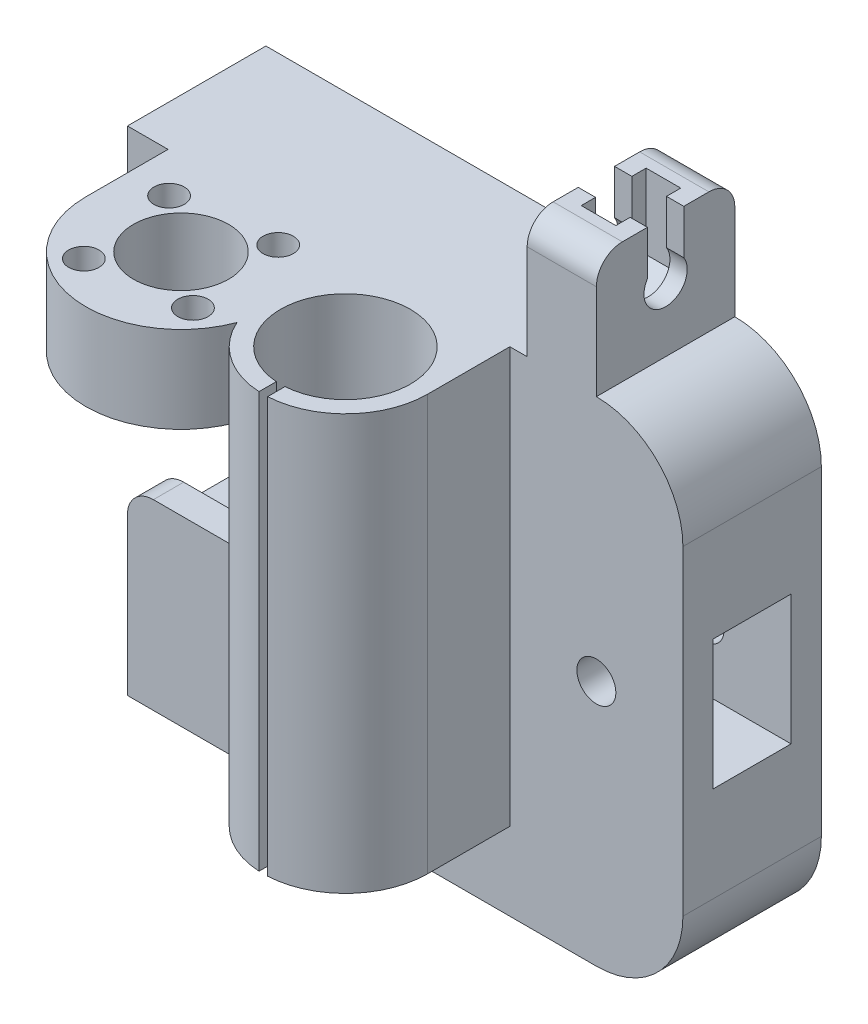
SolidWorks part; units mm, degrees
ref_plane "Front Plane" through (0, 0, 0) normal (0, 0, 1) x (1, 0, 0)
ref_plane "Top Plane" through (0, 0, 0) normal (0, 1, 0) x (1, 0, 0)
ref_plane "Right Plane" through (0, 0, 0) normal (1, 0, 0) x (0, 0, -1)
sketch "Sketch1" plane through (0, 0, 0) normal (0, 1, 0) x (1, 0, 0)
  line L0 (0, 0) -> (64.191, 0)
  line L1 (64.191, 0) -> (64.191, -16)
  line L2 (34.191, -32.9833) -> (34.191, -34.9868)
  line L3 (0, 0) -> (0, -16)
  line L4 (15.691, -25.5) -> (34.691, -25.5) construction
  line L5 (15.691, -25.5) -> (15.691, 0) construction
  line L6 (15.691, -25.5) -> (15.691, -33.5) construction
  line L7 (10.7657, -31.8041) -> (20.6163, -19.1959) construction
  line L8 (9.3869, -20.5747) -> (21.9951, -30.4253) construction
  line L9 (35.191, -32.9833) -> (35.191, -34.9868)
  line L10 (34.691, -25.5) -> (34.691, -32.9833) construction
  line L11 (34.191, -32.9833) -> (35.191, -32.9833) construction
  line L12 (34.191, -34.9868) -> (35.191, -34.9868) construction
  line L13 (64.191, -16) -> (44.191, -16)
  line L14 (44.191, -16) -> (44.191, -25.5)
  line L15 (0, -16) -> (4.691, -16)
  line L16 (4.691, -16) -> (4.691, -25.5)
  circle A0 centre (15.691, -25.5) radius 5.5
  arc A1 (35.191, -32.9833) -> (34.191, -32.9833) centre (34.691, -25.5) ccw
  arc A2 (35.191, -34.9868) -> (44.191, -25.5) centre (34.691, -25.5) ccw
  circle A3 centre (15.691, -25.5) radius 8 construction
  circle A4 centre (10.7657, -31.8041) radius 1.75
  circle A5 centre (9.3869, -20.5747) radius 1.75
  circle A6 centre (20.6163, -19.1959) radius 1.75
  circle A7 centre (21.9951, -30.4253) radius 1.75
  arc A8 (4.691, -25.5) -> (26.0002, -29.3367) centre (15.691, -25.5) ccw
  arc A9 (26.0002, -29.3367) -> (34.191, -34.9868) centre (34.691, -25.5) ccw
  dimension "D1" = 19
  dimension "D2" = 15
  dimension "D3" = 11
  dimension "D5" = 2
  dimension "D6" = 16
  dimension "D7" = 38
  dimension "D8" = 3.5
  dimension "D9" = 22
  dimension "D10" = 1
  dimension "D4" = 25.5
  dimension "D11" = 16
  dimension "D12" = 20
  dimension "D13" = 4.691
extrude "Boss-Extrude1" add sketch "Sketch1" along normal mid plane 57 contours A8 A2 L0 | A2 A8 A0 A4 A5 A6 A7 | A8 A2 L2 A1 L9 | A2 A8 region at (29.3649, 0, 12.581)
sketch "Sketch2" plane through (0, 0, 16) normal (0, 0, 1) x (1, 0, 0)
  line L0 (4.691, 28.5) -> (4.691, -28.5) construction
  line L1 (4.691, 18.5) -> (26.0002, 18.5)
  line L2 (4.691, 18.5) -> (4.691, -28.5)
  line L3 (4.691, -28.5) -> (44.191, -28.5)
  line L5 (26.0002, 28.5) -> (4.691, 28.5) construction
  line L6 (26.0002, 18.5) -> (26.0002, -19.5)
  line L7 (26.0002, -19.5) -> (44.191, -19.5)
  line L8 (44.191, 28.5) -> (44.191, -28.5) construction
  line L9 (44.191, -19.5) -> (44.191, -28.5)
  dimension "D1" = 10
  dimension "D2" = 9
  dimension "D3" = 21.3092
extrude "Cut-Extrude1" cut sketch "Sketch2" along normal through all
sketch "Sketch3" plane through (0, 0, 0) normal (-1, 0, 0) x (0, 0, 1)
  line L0 (8, 28.5) -> (8, 12.5) construction
  line L1 (3.5, 12.5) -> (12.5, 12.5)
  line L2 (3.5, 12.5) -> (3.5, -12.5)
  line L3 (3.5, -12.5) -> (12.5, -12.5)
  line L4 (12.5, 12.5) -> (12.5, -12.5)
  line L5 (0, 28.5) -> (16, 28.5) construction
  line L6 (0, 0) -> (3.5, 0) construction
  line L7 (0, 28.5) -> (0, -28.5) construction
  line L8 (0, -28.5) -> (16, -28.5) construction
  dimension "D1" = 3.5
  dimension "D2" = 16
  dimension "D3" = 25
extrude "Cut-Extrude2" cut sketch "Sketch3" against normal blind 28
sketch "Sketch4" plane through (0, 0, 0) normal (-1, 0, 0) x (0, 0, 1)
  line L0 (16, 28.5) -> (16, -28.5) construction
  line L1 (0, 7.4) -> (16, 7.4)
  line L2 (0, 7.4) -> (0, -7.4)
  line L3 (0, -7.4) -> (16, -7.4)
  line L4 (16, 7.4) -> (16, -7.4)
  point P4 (0, 0)
  point P9 (8, 7.4)
  dimension "D1" = 14.8
extrude "Cut-Extrude3" cut sketch "Sketch4" against normal up to surface (26.0002 mm away) up to face at (26.0002, -0.5, 22.6683)
hole_wizard "M4 Clearance Hole1" positions "3DSketch1" profile "Sketch5" hole size "M4" standard "ANSI Metric" end condition through all
sketch3d "3DSketch1"
  line L0 (54.191, 0, 16) -> (64.191, 0, 16) construction
  line L6 (64.191, 28.5, 16) -> (64.191, -28.5, 16) construction
  point P0 (54.191, 0, 16)
  dimension "D1" = 10
sketch "Sketch5" plane through (54.191, 0, 16) normal (1, 0, 0) x (0, -1, 0)
  line L0 (0, 0) -> (0, 16)
  line L1 (0, 16) -> (2.25, 16)
  line L2 (2.25, 16) -> (2.25, 0)
  line L5 (2.25, 0) -> (0, 0)
  line L11 (0, -6.35) -> (0, 107.95) construction
  dimension "Thru Hole Dia." = 4.5
  dimension "Thru Hole Depth" = 16
sketch "Sketch6" plane through (0, 0, 0) normal (-1, 0, 0) x (0, 0, 1)
  line L0 (8, -22.5) -> (8, 22.5) construction
  line L1 (8, 22.5) -> (8, 28.5) construction
  line L2 (8, -22.5) -> (8, -28.5) construction
  line L3 (0, -28.5) -> (16, -28.5) construction
  line L4 (0, 28.5) -> (16, 28.5) construction
  circle A0 centre (8, 22.5) radius 4.1
  circle A1 centre (8, -22.5) radius 4.1
  dimension "D1" = 45
  dimension "D2" = 8.2
extrude "Cut-Extrude4" cut sketch "Sketch6" against normal blind 20 contours A1 | A0 | A0 region at (0, 22.5, 8) region at (0, -22.5, 8)
sketch "Sketch7" plane through (28, 0, 0) normal (-1, 0, 0) x (0, 0, 1)
  line L0 (0, 0) -> (3.5, 0) construction
  line L1 (3.5, 7.5) -> (12.5, 7.5)
  line L2 (3.5, 7.5) -> (3.5, -7.5)
  line L3 (3.5, -7.5) -> (12.5, -7.5)
  line L4 (12.5, 7.5) -> (12.5, -7.5)
  line L5 (8, 7.5) -> (8, 12.5) construction
  line L6 (12.5, 12.5) -> (3.5, 12.5) construction
  line L7 (12.5, -12.5) -> (12.5, 12.5) construction
  dimension "D1" = 15
extrude "Cut-Extrude5" cut sketch "Sketch7" against normal through all
fillet "Fillet1" radius 10 2 edges at (64.191, 28.5, 8) (64.191, -28.5, 8)
fillet "Fillet2" radius 3 4 edges at (0, -7.4, 14.25) (0, -7.4, 1.75) (0, 7.4, 14.25) (0, 7.4, 1.75)
sketch "Sketch11" plane through (0, 28.5, 0) normal (0, 1, 0) x (1, 0, 0)
  line L0 (0, 0) -> (54.191, 0) construction
  line L1 (46.191, 0) -> (54.191, 0)
  line L2 (46.191, 0) -> (46.191, -16)
  line L3 (46.191, -16) -> (54.191, -16)
  line L4 (54.191, 0) -> (54.191, -16)
  line L5 (54.191, -16) -> (44.191, -16) construction
  dimension "D1" = 8
extrude "Boss-Extrude2" add sketch "Sketch11" along normal blind 14
sketch "Sketch12" plane through (54.191, 0, 0) normal (1, 0, 0) x (0, 0, -1)
  line L0 (-8, 36) -> (-8, 28.5) construction
  line L1 (-16, 28.5) -> (0, 28.5) construction
  line L2 (-11.75, 38.1651) -> (-11.75, 43.5)
  line L3 (-8, 40.3301) -> (-11.75, 38.1651)
  line L4 (-11.75, 38.1651) -> (-11.75, 33.8349)
  line L5 (-11.75, 33.8349) -> (-8, 31.6699)
  line L6 (-8, 31.6699) -> (-4.25, 33.8349)
  line L7 (-4.25, 33.8349) -> (-4.25, 38.1651)
  line L8 (-4.25, 38.1651) -> (-8, 40.3301)
  line L9 (-11.75, 43.5) -> (-4.25, 43.5)
  line L10 (-4.25, 43.5) -> (-4.25, 38.1651)
  circle A0 centre (-8, 36) radius 2.5
  circle A1 centre (-8, 36) radius 3.75 construction
  line M9 (0, 42.5) -> (-16, 42.5)
  dimension "D1" = 7.5
  dimension "D2" = 5
  dimension "D3" = 7.5
  dimension "D4" = 15
extrude "Cut-Extrude6" cut sketch "Sketch12" against normal blind 4 from offset 2 contours A0 | L7 L8 L3 L4 L5 L6 A0 | L10 L2 L3 L8 M9 region at (54.191, 40.8137, 8) region at (54.191, 39.1484, 9.8177) region at (54.191, 36, 8) offset against normal yes
sketch "Sketch13" plane through (54.191, 0, 0) normal (1, 0, 0) x (0, 0, -1)
  line L0 (-10.1, 42.5) -> (-5.9, 42.5)
  line L1 (-5.9, 42.5) -> (-5.9, 37.3565)
  line L2 (-10.1, 42.5) -> (-10.1, 37.3565)
  line L3 (-16, 42.5) -> (0, 42.5) construction
  circle A0 centre (-8, 36) radius 2.5 construction
  circle A1 centre (-8, 36) radius 2.5
  point P6 (-8, 42.5)
  point P10 (0, 0)
  point P11 (0, 0)
  line M3 (0, 42.5) -> (-16, 42.5)
  dimension "D1" = 4.2
extrude "Cut-Extrude7" cut sketch "Sketch13" against normal through all contours A1 | A1 L1 L2 M3 region at (54.191, 40.3191, 8) region at (54.191, 36, 8)
fillet "Fillet3" radius 3 2 edges at (50.191, 42.5, 0) (50.191, 42.5, 16)
